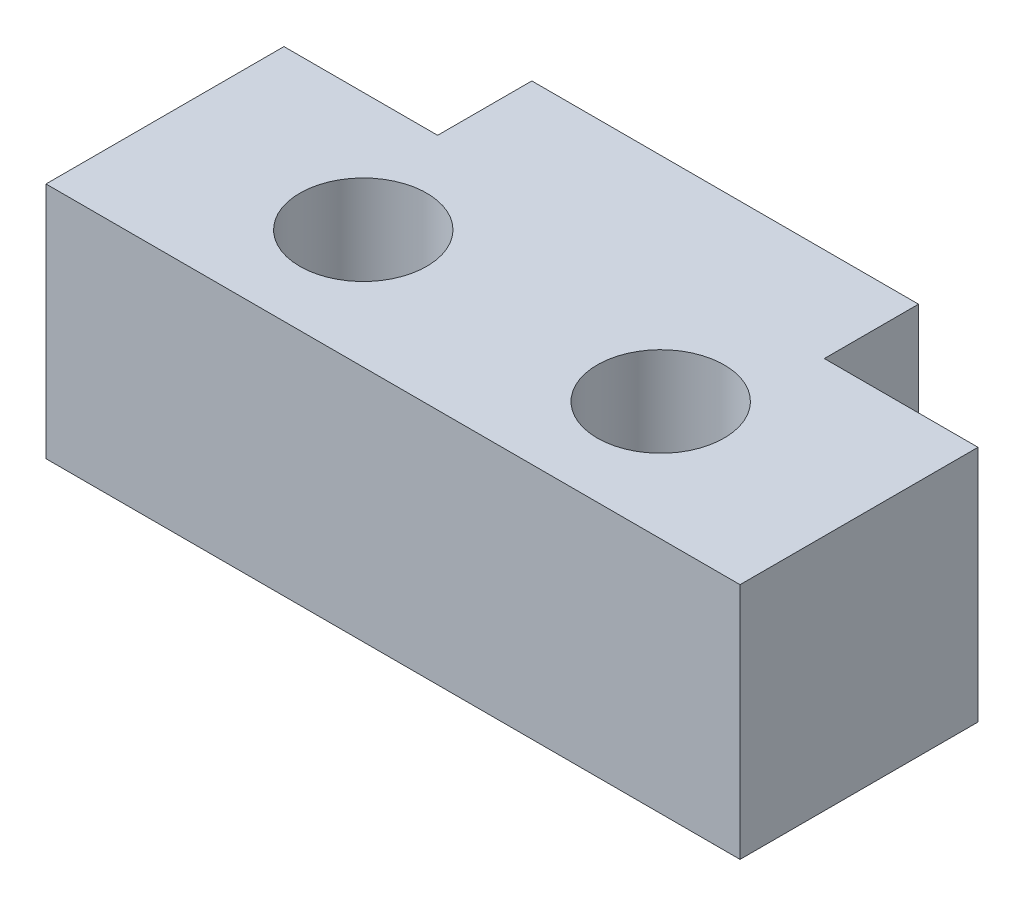
SolidWorks part; units mm, degrees
material "K110"
ref_plane "Front Plane" through (0, 0, 0) normal (0, 0, 1) x (1, 0, 0)
ref_plane "Top Plane" through (0, 0, 0) normal (0, 1, 0) x (1, 0, 0)
ref_plane "Right Plane" through (0, 0, 0) normal (1, 0, 0) x (0, 0, -1)
sketch "Sketch1" plane through (0, 0, 0) normal (0, 0, 1) x (1, 0, 0)
  line L1 (-17.5, -6) -> (17.5, -6)
  line L2 (-17.5, -6) -> (-17.5, 6)
  line L3 (-17.5, 6) -> (17.5, 6)
  line L4 (17.5, -6) -> (17.5, 6)
  line L5 (-17.5, -6) -> (17.5, 6) construction
  line L6 (-17.5, 6) -> (17.5, -6) construction
  point P0 (0, 0)
  dimension "D1" = 35
  dimension "D2" = 12
extrude "Boss-Extrude1" add sketch "Sketch1" along normal mid plane 12
sketch "Sketch3" plane through (0, 6, 0) normal (0, 1, 0) x (1, 0, 0)
  line L0 (17.5, 6) -> (-17.5, 6) construction
  line L1 (-9.75, 6) -> (9.75, 6)
  line L2 (-9.75, 6) -> (-9.75, 10.75)
  line L3 (-9.75, 10.75) -> (9.75, 10.75)
  line L4 (9.75, 6) -> (9.75, 10.75)
  point P6 (0, 6)
  dimension "D1" = 19.5
  dimension "D2" = 4.75
extrude "Boss-Extrude2" add sketch "Sketch3" against normal up to surface (12 mm away) up to face at (0, -6, 0)
sketch "Sketch4" plane through (0, 6, 0) normal (0, 1, 0) x (1, 0, 0)
  line L0 (0, -6) -> (0, 10.75) construction
  line L1 (17.5, -6) -> (-17.5, -6) construction
  line L2 (9.75, 10.75) -> (-9.75, 10.75) construction
  circle A0 centre (-7.5, 0) radius 5
  circle A1 centre (7.5, 0) radius 5
  dimension "D1" = 10
  dimension "D2" = 15
hole_wizard "M6 Clearance Hole1" positions "Sketch7" profile "Sketch6" hole size "M6" standard "ISO" end condition through all
sketch "Sketch7" plane through (0, 6, 0) normal (0, 1, 0) x (1, 0, 0)
  point P0 (-7.5, 0)
  point P3 (7.5, 0)
sketch "Sketch6" plane through (-7.5, 6, 0) normal (1, 0, 0) x (0, 0, 1)
  line L0 (0, 0) -> (0, 12)
  line L1 (0, 12) -> (3.2, 12)
  line L2 (3.2, 12) -> (3.2, 0)
  line L5 (3.2, 0) -> (0, 0)
  line L11 (0, -6.35) -> (0, 107.95) construction
  dimension "Thru Hole Dia." = 6.4
  dimension "Thru Hole Depth" = 12
